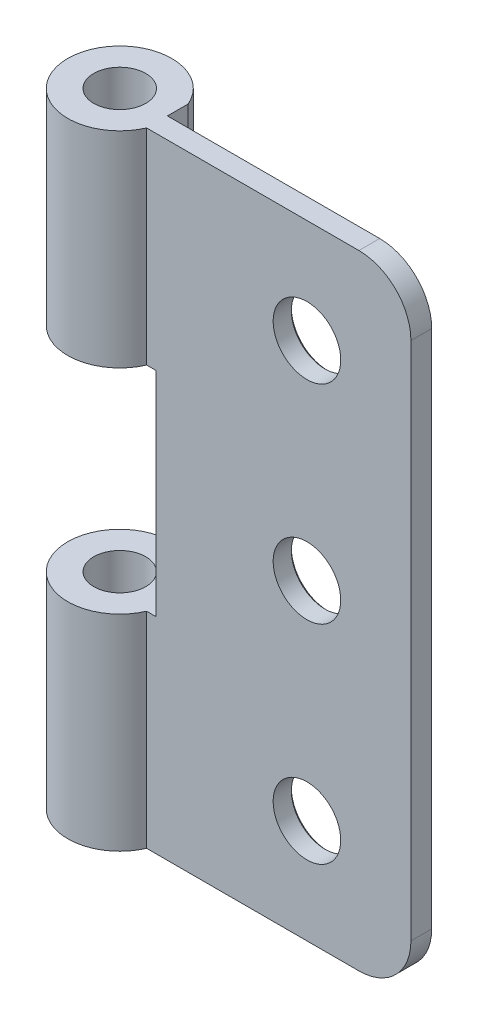
SolidWorks part; units mm, degrees
material "AISI 316 Stainless Steel Sheet (SS)"
ref_plane "Front Plane" through (0, 0, 0) normal (0, 0, 1) x (1, 0, 0)
ref_plane "Top Plane" through (0, 0, 0) normal (0, 1, 0) x (1, 0, 0)
ref_plane "Right Plane" through (0, 0, 0) normal (1, 0, 0) x (0, 0, -1)
sketch "Sketch1" plane through (0, 0, 0) normal (0, 1, 0) x (1, 0, 0)
  line L0 (0, 0) -> (31.9054, 0) construction
  line L1 (30, 2) -> (30, -2)
  line L2 (30, -2) -> (4.5826, -2)
  line L3 (5.5, 2) -> (5.5, -2)
  line L4 (4.5826, 2) -> (4.5826, 0)
  line L5 (30, 2) -> (4.5826, 2)
  line L6 (4.5826, 0) -> (5.5, 0)
  circle A0 centre (0, 0) radius 2.5
  arc A1 (4.5826, 2) -> (4.5826, -2) centre (0, 0) ccw
  dimension "D1" = 4
  dimension "D3" = 5
  dimension "D4" = 10
  dimension "D5" = 30
  dimension "D6" = 5.5
extrude "Boss-Extrude1" add sketch "Sketch1" along normal mid plane 60 contours L0 L3 L2 L1 | A0 L3 L5 A1 L2 region at (5.0413, 0, 0.145) region at (17.75, 0, 1)
extrude "Cut-Extrude1" cut sketch "Sketch1<3>" against normal mid plane 20.5 contours A0 L3 L5 A1 L2 region at (5.0413, 0, 1.855)
sketch "Sketch1<3>" plane through (0, 0, 0) normal (0, 1, 0) x (1, 0, 0) same geometry as "Sketch1"
hole_wizard "Ø6.5 (6.5) Diameter Hole1" positions "Sketch2" profile "Sketch3" hole size "Ø6.5" standard "ANSI Metric" end condition through all
sketch "Sketch2" plane through (0, 0, 0) normal (0, 0, -1) x (-1, 0, 0)
  line L0 (-20, -30) -> (-20, 30) construction
  line L3 (-4.5826, 30) -> (-30, 30) construction
  line L4 (-4.5826, -30) -> (-30, -30) construction
  point P0 (-20, -20)
  point P2 (-20, 0)
  point P4 (-20, 20)
  dimension "D1" = 20
  dimension "D2" = 20
  dimension "D3" = 20
sketch "Sketch3" plane through (20, -20, 0) normal (1, 0, 0) x (0, 1, 0)
  line L0 (0, 0) -> (0, 5)
  line L1 (0, 5) -> (3.25, 5)
  line L2 (3.25, 5) -> (3.25, 0.25)
  line L3 (3.25, 0.25) -> (3.5, 0)
  line L5 (3.5, 0) -> (0, 0)
  line L6 (-3.25, 0.25) -> (-3.5, 0) construction
  line L11 (0, -6.35) -> (0, 107.95) construction
  dimension "Thru Hole Dia." = 6.5
  dimension "Thru Hole Depth" = 5
  dimension "Near C'Sink Dia." = 7
  dimension "Near C'Sink Angle" = 90
fillet "Fillet1" radius 5 2 edges at (30, 30, 1) (30, -30, 1)
